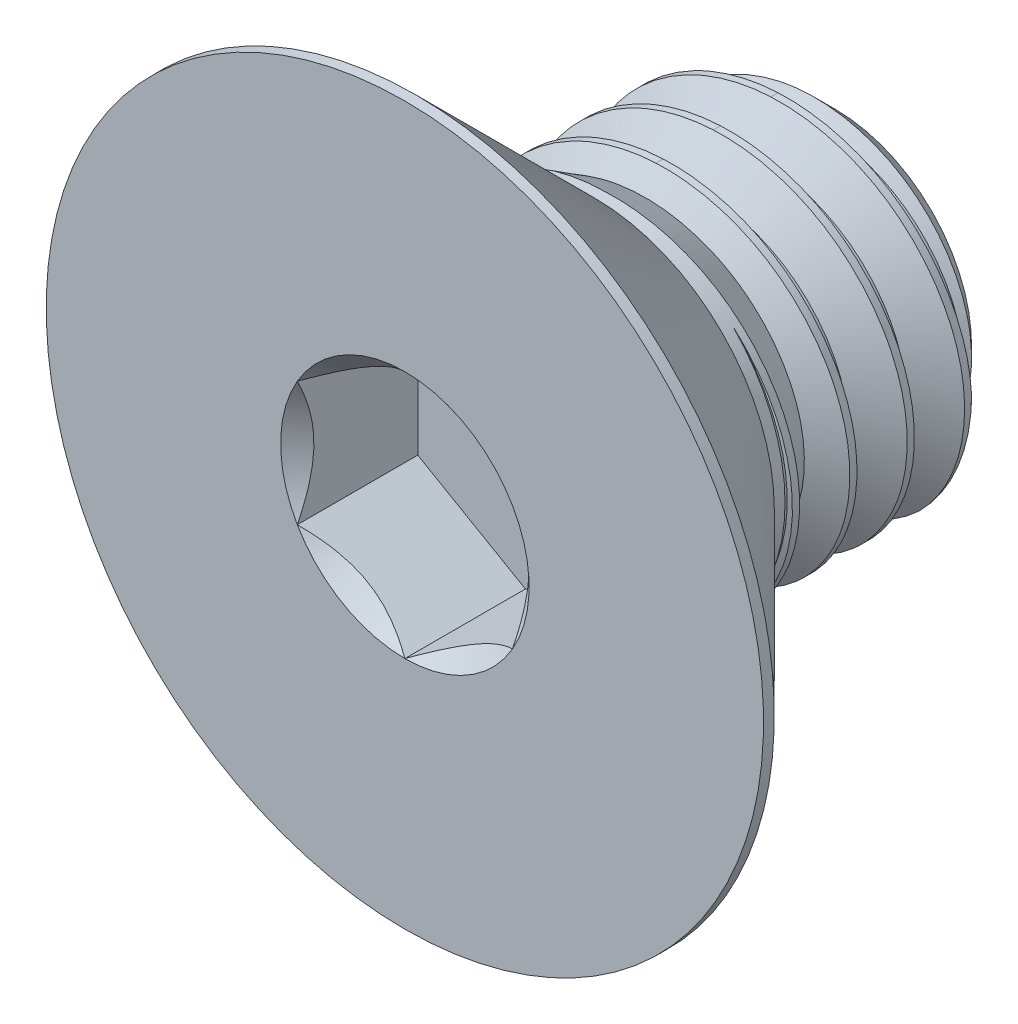
SolidWorks part; units mm, degrees
ref_plane "Front" through (0, 0, 0) normal (0, 0, 1) x (1, 0, 0)
ref_plane "Top" through (0, 0, 0) normal (0, 1, 0) x (1, 0, 0)
ref_plane "Right" through (0, 0, 0) normal (1, 0, 0) x (0, 0, -1)
sketch "Sketch1" plane through (0, 0, 0) normal (0, 0, 1) x (1, 0, 0)
  line L1 (1.5, 0.866) -> (0, 1.7321)
  line L8 (0, 1.7321) -> (-1.5, 0.866)
  line L9 (-1.5, 0.866) -> (-1.5, -0.866)
  line L10 (-1.5, -0.866) -> (0, -1.7321)
  line L11 (0, -1.7321) -> (1.5, -0.866)
  line L12 (1.5, -0.866) -> (1.5, 0.866)
  circle A0 centre (0, 0) radius 1.5 construction
  circle A1 centre (0, 0) radius 5
  point P7 (0, 5)
  dimension "Head Dia" = 10
  dimension "Hex" = 3
sketch "Sketch2" plane through (0, 0, 0) normal (1, 0, 0) x (0, 0, -1)
  line L2 (0, 0) -> (3.2, 0) construction
  line L3 (3.2, 0) -> (3.2, 2.5)
  line L6 (3.2, 2.5) -> (0, 2.5)
  line L8 (0, 2.5) -> (-0.15, 2.5)
  line L9 (-0.15, 2.5) -> (-2.65, 5)
  line L11 (-2.65, 5) -> (-2.8, 5)
  line L13 (-2.8, 5) -> (-2.8, 0)
  line L14 (-2.8, 0) -> (0, 0) construction
  line L15 (3.15, 2.5866) -> (3.55, 1.8938) construction
  line L16 (3.55, 1.8938) -> (3.95, 2.5866) construction
  line L17 (3.95, 2.5866) -> (3.15, 2.5866) construction
  line L18 (3.175, 2.5433) -> (3.925, 2.5433)
  line L19 (3.925, 2.5433) -> (3.6, 1.9804)
  line L20 (3.6, 1.9804) -> (3.5, 1.9804)
  line L21 (3.5, 1.9804) -> (3.175, 2.5433)
  line L22 (3.55, 1.9804) -> (3.55, 1.8938) construction
  line L23 (3.2, 2.5) -> (3.9, 2.5) construction
  line L24 (3.55, 2.5866) -> (3.55, 2.5) construction
  line L25 (3.2, 1.9) -> (2.6, 2.5)
  line L26 (3.2, -2.5) -> (0, -2.5)
  point P28 (3.55, 2.5433)
  point P32 (2, -2.5)
  point P33 (-1.12, 0)
  point P35 (-2.8, 5)
  dimension "Dia" = 5
  dimension "Head Ht" = 2.8
  dimension "D2" = 45
  dimension "Lg" = 6
  dimension "Pitch" = 0.8
  dimension "D3" = 0.1
  dimension "D1" = 45
  dimension "D4" = 0.6
  dimension "D5" = 1.2
  dimension "D6" = 1.68
sketch "Sketch7" plane through (0, 0, 0) normal (1, 0, 0) x (0, 0, -1)
  line L2 (-2.8, 0) -> (-2.8, 5)
  line L3 (-2.8, 5) -> (-2.65, 5)
  line L5 (-2.65, 5) -> (-0.15, 2.5)
  line L6 (-0.15, 2.5) -> (2.6, 2.5)
  line L8 (2.6, 2.5) -> (3.2, 1.9)
  line L9 (3.2, 1.9) -> (3.2, 0)
  line L11 (3.2, 0) -> (-2.8, 0)
revolve "Revolve2" add sketch "Sketch7" angle 360 mid plane about L11
sketch "Sketch5" plane through (0, 0, 2.8) normal (0, 0, 1) x (1, 0, 0)
  line L0 (1.5, -0.866) -> (1.5, 0.866) construction
  line L1 (0, -1.7321) -> (1.5, -0.866) construction
  line L2 (-1.5, -0.866) -> (0, -1.7321) construction
  line L3 (-1.5, 0.866) -> (-1.5, -0.866) construction
  line L4 (0, 1.7321) -> (-1.5, 0.866) construction
  line L5 (1.5, 0.866) -> (0, 1.7321) construction
  line L6 (1.5, -0.866) -> (1.5, 0.866)
  line L7 (0, -1.7321) -> (1.5, -0.866)
  line L8 (-1.5, -0.866) -> (0, -1.7321)
  line L9 (-1.5, 0.866) -> (-1.5, -0.866)
  line L10 (0, 1.7321) -> (-1.5, 0.866)
  line L11 (1.5, 0.866) -> (0, 1.7321)
extrude "Cut-Extrude2" cut sketch "Sketch5" against normal up to vertex (1.68 mm away) up to point (0, 0, 1.12)
sketch "Sketch6" plane through (0, 0, 2.8) normal (0, 0, 1) x (1, 0, 0)
  circle A0 centre (0, 0) radius 1.7321
extrude "Cut-Extrude3" cut sketch "Sketch6" against normal up to vertex (1.68 mm away) draft 45 up to point (0, 0, 1.12)
sketch "Sketch3" plane through (0, 0, -3.2) normal (0, 0, -1) x (-1, 0, 0)
  circle A0 centre (0, 0) radius 2.5
split "Split1" trim tools "Front" bodies to split 113 resulting bodies 125 126
curve "Helix/Spiral1" pitch 0.8 height 4 radius 2.5 centre (0, 0, -3.2) axis (0, 0, 1) start towards (0, 1, 0)
sketch "Sketch8" plane through (0, 0, 0) normal (1, 0, 0) x (0, 0, -1)
  line L0 (3.175, 2.5433) -> (3.925, 2.5433) construction
  line L1 (3.5, 1.9804) -> (3.175, 2.5433) construction
  line L2 (3.6, 1.9804) -> (3.5, 1.9804) construction
  line L3 (3.925, 2.5433) -> (3.6, 1.9804) construction
  line L4 (3.175, 2.5433) -> (3.925, 2.5433)
  line L5 (3.5, 1.9804) -> (3.175, 2.5433)
  line L6 (3.6, 1.9804) -> (3.5, 1.9804)
  line L7 (3.925, 2.5433) -> (3.6, 1.9804)
sweep "Cut-Sweep1" cut profiles "Sketch8" path "Helix/Spiral1" align with end faces yes
sketch "Sketch9" plane through (0, 0, 0) normal (0, 0, 1) x (1, 0, 0)
  circle A0 centre (0, 0) radius 2.5
extrude "Boss-Extrude1" add sketch "Sketch9" against normal up to vertex (3.2 mm away) draft 30.9 up to point (0, 0, -3.2)
equation "\"D3@Helix/Spiral1\" =  ( \"Lg@Sketch2\" - \"Head Ht@Sketch2\" )  + \"Pitch@Sketch2\""
equation "\"D1\"= \"Head Ht@Sketch2\" * .7"
equation "\"D1\"= \"D1\""
equation "\"D4@Helix/Spiral1\" = \"Pitch@Sketch2\""
equation "\"D3@Sketch2\" = \"Pitch@Sketch2\" / 8"
equation "\"D4@Sketch2\" = \"Pitch@Sketch2\" * 0.75"
equation "\"D5@Sketch2\" = \"Pitch@Sketch2\" * 1.5"
equation "\"D6@Sketch2\" = \"Head Ht@Sketch2\" * 0.6"
